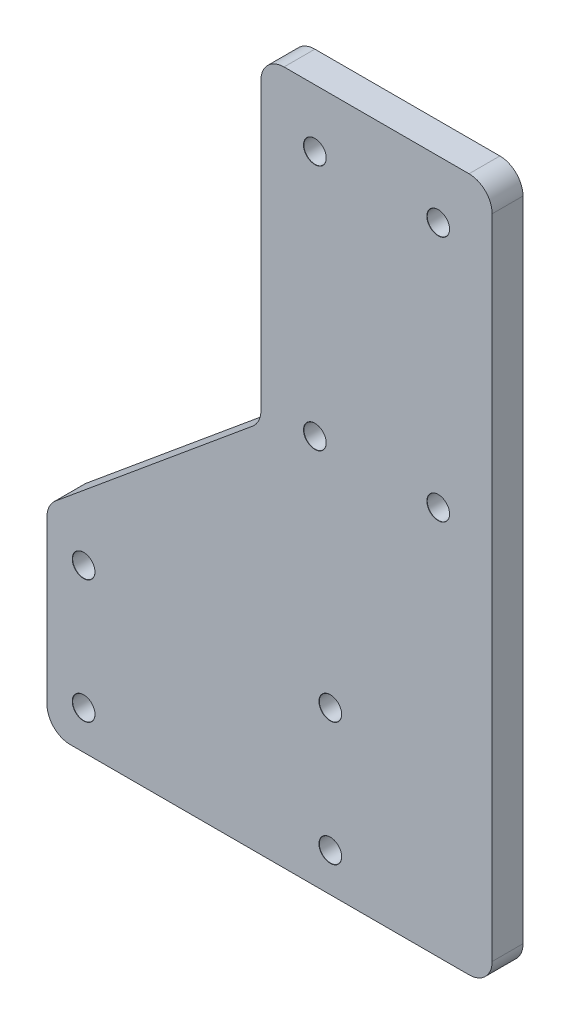
SolidWorks part; units mm, degrees
ref_plane "前视基准面" through (0, 0, 0) normal (0, 0, 1) x (1, 0, 0)
ref_plane "上视基准面" through (0, 0, 0) normal (0, 1, 0) x (1, 0, 0)
ref_plane "右视基准面" through (0, 0, 0) normal (1, 0, 0) x (0, 0, -1)
sketch "草图1" plane through (0, 0, 0) normal (0, 0, 1) x (1, 0, 0)
  line L0 (0, 0) -> (-41.5, 0)
  line L1 (-41.5, 0) -> (-41.5, 25.5)
  line L2 (-41.5, 25.5) -> (-13.75, 48.5)
  line L6 (14.05, -11.5) -> (-49.0563, -11.5) construction
  line L7 (-13.75, 48.5) -> (-13.75, 90)
  line L8 (-13.75, 90) -> (16.25, 90)
  line L9 (16.25, 90) -> (16.25, 0)
  line L10 (-92.1756, 35) -> (57.8057, 35) construction
  line L11 (-105.9645, 43.75) -> (59.2906, 43.75) construction
  line L12 (1.25, -9) -> (1.25, 87.7198) construction
  line L13 (0, 0) -> (16.25, 0)
  dimension "D1" = 41.5
  dimension "D2" = 90
  dimension "D3" = 25.5
  dimension "D4" = 30
  dimension "D5" = 41.5
  dimension "D6" = 35
  dimension "D7" = 8.75
extrude "凸台-拉伸1" add sketch "草图1" along normal blind 4
hole_wizard "M2.5 间隙孔1" positions "草图2" profile "草图3" hole size "M2.5" standard "ISO" end condition through all
sketch "草图2" plane through (0, 0, 4) normal (0, 0, 1) x (1, 0, 0)
  line L0 (-20.75, 0) -> (-20.75, 28.9161) construction
  line L1 (-41.5, 0) -> (16.25, 0) construction
  line L2 (-36.75, 21) -> (-4.75, 21) construction
  line L3 (1.25, 90) -> (1.25, 32.5659) construction
  line L10 (1.25, -11.5) -> (1.25, -9) construction
  line L12 (16.25, 90) -> (-13.75, 90) construction
  point P6 (-36.75, 5)
  point P8 (-36.75, 21)
  point P12 (-4.75, 5)
  point P13 (-4.75, 21)
  point P44 (-6.75, 82.5)
  point P47 (9.25, 82.5)
  point P51 (-6.75, 50.5)
  point P54 (9.25, 50.5)
  dimension "D1" = 16
  dimension "D2" = 16
  dimension "D3" = 0
  dimension "D4" = 5
  dimension "D5" = 7.5
  dimension "D6" = 32
  dimension "D7" = 8
  dimension "D8" = 16
  dimension "D9" = 8
  dimension "D10" = 8
  dimension "D11" = 16
  dimension "D12" = 32
sketch "草图3" plane through (9.25, 50.5, 4) normal (1, 0, 0) x (0, -1, 0)
  line L0 (0, 0) -> (0, 4)
  line L1 (0, 4) -> (1.45, 4)
  line L2 (1.45, 4) -> (1.45, 0.025)
  line L3 (1.45, 0.025) -> (1.475, 0)
  line L5 (1.475, 0) -> (0, 0)
  line L6 (-1.45, 0.025) -> (-1.475, 0) construction
  line L11 (0, -6.35) -> (0, 107.95) construction
  dimension "通孔孔直径" = 2.9
  dimension "通孔孔深度" = 4
  dimension "近端锥形沉头孔直径" = 2.95
  dimension "近端锥形沉头孔角度" = 90
fillet "圆角2" radius 3 6 edges at (16.25, 0, 2) (-41.5, 0, 2) (-41.5, 25.5, 2) (-13.75, 48.5, 2) (-13.75, 90, 2) (16.25, 90, 2)
